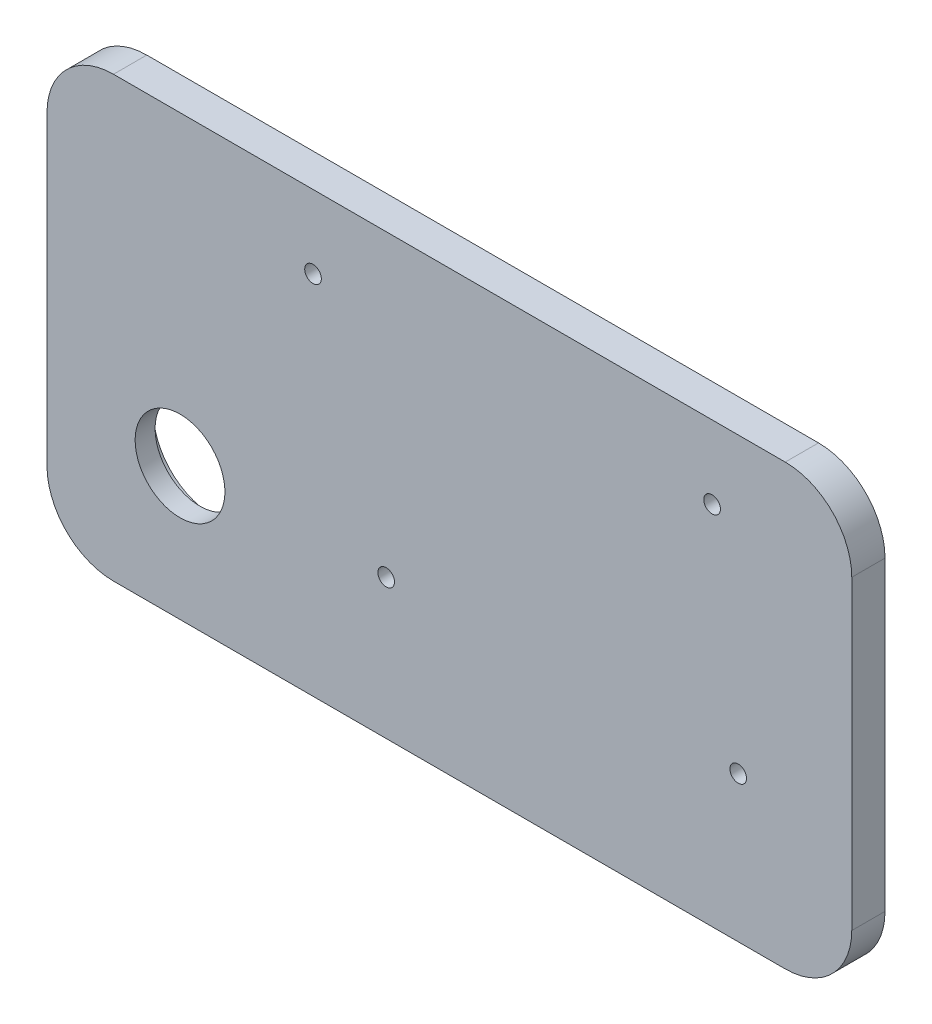
SolidWorks part; units mm, degrees
ref_plane "Front Plane" through (0, 0, 0) normal (0, 0, 1) x (1, 0, 0)
ref_plane "Top Plane" through (0, 0, 0) normal (0, 1, 0) x (1, 0, 0)
ref_plane "Right Plane" through (0, 0, 0) normal (1, 0, 0) x (0, 0, -1)
sketch "Sketch1" plane through (0, 0, 0) normal (0, 0, 1) x (1, 0, 0)
  line L0 (-50.5, 20) -> (50.5, -26) construction
  line L1 (-52.5, -25) -> (52.5, -25) construction
  line L2 (-52.5, -25) -> (-52.5, 25) construction
  line L3 (-52.5, 25) -> (52.5, 25) construction
  line L4 (52.5, -25) -> (52.5, 25) construction
  line L5 (-52.5, -25) -> (52.5, 25) construction
  line L6 (-52.5, 25) -> (52.5, -25) construction
  line L7 (-50.5, -36) -> (50.5, -36)
  line L8 (-60.5, -26) -> (-60.5, 20)
  line L9 (-50.5, 30) -> (50.5, 30)
  line L10 (60.5, -26) -> (60.5, 20)
  line L11 (50.5, 20) -> (-50.5, -26) construction
  line L12 (-57.5, -26) -> (-57.5, 20) construction
  line L13 (-50.5, 27) -> (50.5, 27) construction
  line L14 (57.5, -26) -> (57.5, 20) construction
  line L15 (-50.5, -33) -> (50.5, -33) construction
  line L16 (0, 0) -> (0, -3) construction
  line L17 (0, 25) -> (0, 30) construction
  line L18 (-57.5, -3) -> (-52.5, -3) construction
  arc A0 (50.5, 30) -> (60.5, 20) centre (50.5, 20) cw
  arc A1 (50.5, -36) -> (60.5, -26) centre (50.5, -26) ccw
  arc A2 (-50.5, -36) -> (-60.5, -26) centre (-50.5, -26) cw
  arc A3 (-60.5, 20) -> (-50.5, 30) centre (-50.5, 20) cw
  arc A4 (-50.5, -33) -> (-57.5, -26) centre (-50.5, -26) cw construction
  arc A5 (-57.5, 20) -> (-50.5, 27) centre (-50.5, 20) cw construction
  arc A6 (50.5, 27) -> (57.5, 20) centre (50.5, 20) cw construction
  arc A7 (50.5, -33) -> (57.5, -26) centre (50.5, -26) ccw construction
  point P0 (0, 0)
  point P6 (0, 0)
  dimension "D3" = 10
  dimension "D1" = 105
  dimension "D2" = 50
  dimension "D4" = 5
  dimension "D5" = 3
  dimension "D6" = 3
extrude "Boss-Extrude1" add sketch "Sketch1" along normal blind 5
sketch "Sketch2" plane through (0, 0, 0) normal (0, 0, -1) x (-1, 0, 0)
  line L1 (50.5, -36) -> (-50.5, -36) construction
  line L2 (60.5, 20) -> (60.5, -26) construction
  line L3 (-60.5, -25) -> (60.5, -25) construction
  line L4 (-60.5, -26) -> (-60.5, 20) construction
  circle A0 centre (40.5, -16) radius 6.75
  circle A1 centre (40.5, -16) radius 9 construction
  dimension "D1" = 13.5
  dimension "D3" = 18
  dimension "D2" = 20
  dimension "D4" = 11
extrude "Cut-Extrude1" cut sketch "Sketch2" against normal through all
sketch "Sketch3" plane through (0, 0, 0) normal (0, 0, -1) x (-1, 0, 0)
  line L0 (-39.5, 19) -> (20.5, 19) construction
  circle A0 centre (-39.5, 19) radius 1.25
  circle A1 centre (20.5, 19) radius 1.25
  circle A2 centre (-43.43, -14.1) radius 1.25
  circle A3 centre (9.5, -15) radius 1.25
  point P5 (-9.5, 19)
  dimension "D2" = 2.5
  dimension "D1" = 60
  dimension "D3" = 19
  dimension "D4" = 9.5
  dimension "D5" = 33.1
  dimension "D6" = 3.93
  dimension "D7" = 34
  dimension "D8" = 11
extrude "Cut-Extrude2" cut sketch "Sketch3" against normal blind 5
sketch "Sketch6" plane through (0, 0, 0) normal (0, 0, -1) x (-1, 0, 0)
  circle A0 centre (40.5, -16) radius 9
  dimension "D1" = 18
extrude "Cut-Extrude4" cut sketch "Sketch6" against normal offset from surface (2 mm away) 3 up to face at (-21.75, 19, 5)
